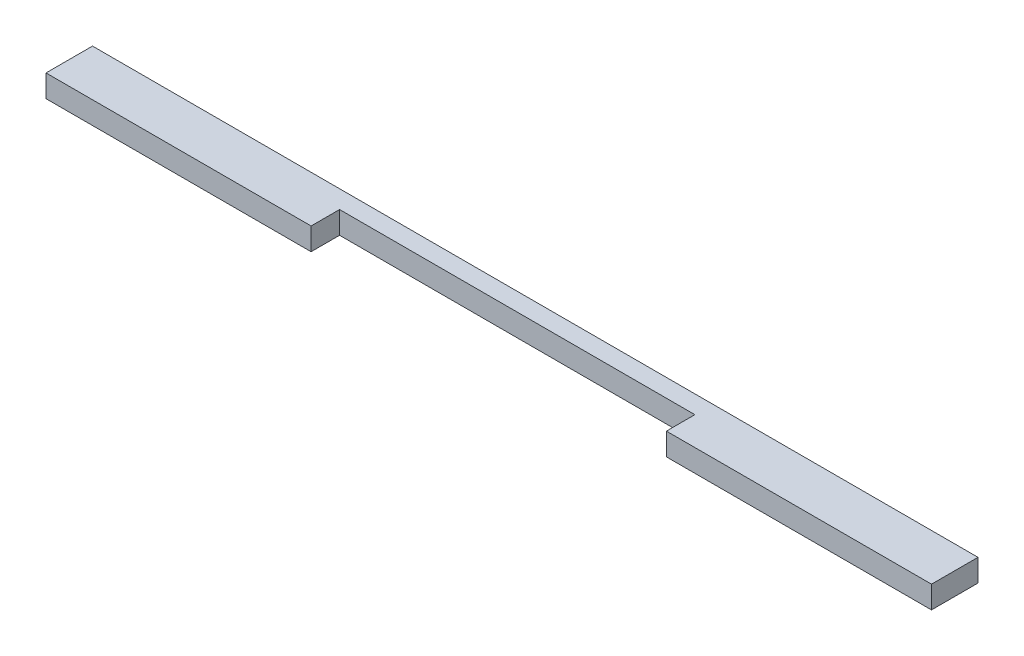
SolidWorks part; units mm, degrees
ref_plane "Front Plane" through (0, 0, 0) normal (0, 0, 1) x (1, 0, 0)
ref_plane "Top Plane" through (0, 0, 0) normal (0, 1, 0) x (1, 0, 0)
ref_plane "Right Plane" through (0, 0, 0) normal (1, 0, 0) x (0, 0, -1)
sketch "Sketch2" plane through (0, 0, 0) normal (0, 1, 0) x (1, 0, 0)
  line L1 (0, 0) -> (476, 0)
  line L2 (0, 0) -> (0, 25)
  line L3 (0, 25) -> (476, 25)
  line L4 (476, 0) -> (476, 25)
  line L5 (142.5, 0) -> (333.5, 0)
  line L6 (142.5, 0) -> (142.5, 15.3096)
  line L7 (142.5, 15.3096) -> (333.5, 15.3096)
  line L8 (333.5, 0) -> (333.5, 15.3096)
  point P9 (476, 12.5)
  dimension "D1" = 25
  dimension "D2" = 476
  dimension "D3" = 142.5
  dimension "D4" = 142.5
extrude "Boss-Extrude1" add sketch "Sketch2" along normal blind 12 contours L8 L1 L4 L3 L2 L6 L7 region at (4.7666, 0, -12.5)
